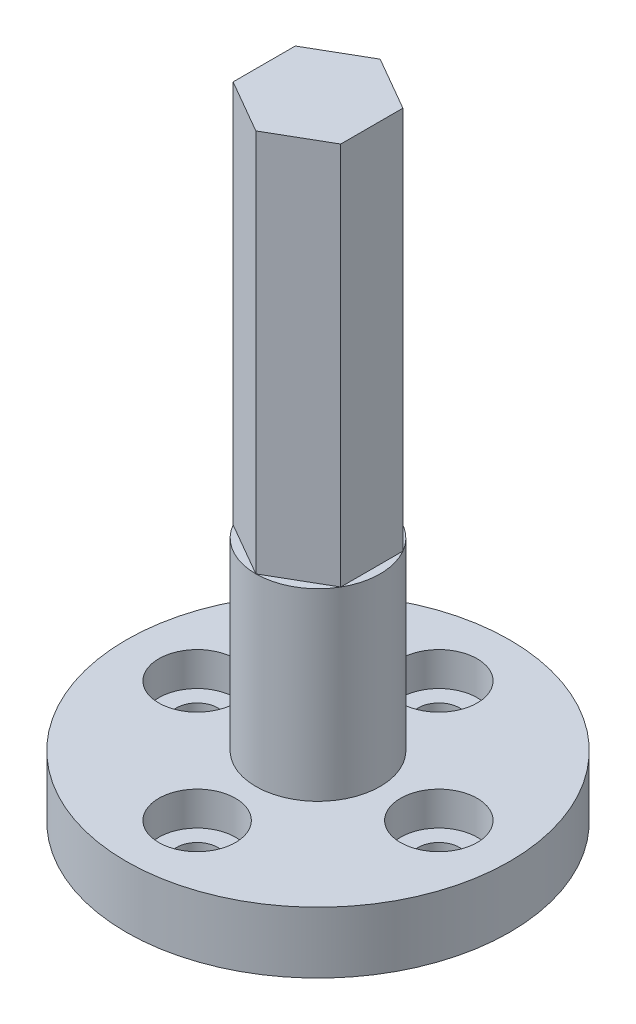
SolidWorks part; units mm, degrees
ref_plane "Alzado" through (0, 0, 0) normal (0, 0, 1) x (1, 0, 0)
ref_plane "Planta" through (0, 0, 0) normal (0, 1, 0) x (1, 0, 0)
ref_plane "Vista lateral" through (0, 0, 0) normal (1, 0, 0) x (0, 0, -1)
sketch "Croquis3" plane through (0, 0, 0) normal (0, 1, 0) x (1, 0, 0)
  circle A0 centre (0, 0) radius 12.5
  dimension "D1" = 25
extrude "Saliente-Extruir1" add sketch "Croquis3" along normal blind 4
sketch "Croquis4" plane through (0, 4, 0) normal (0, 1, 0) x (1, 0, 0)
  circle A0 centre (0, 0) radius 4.05
  dimension "D1" = 8.1
extrude "Saliente-Extruir2" add sketch "Croquis4" along normal blind 37
sketch "Croquis7" plane through (0, 0, 0) normal (0, -1, 0) x (1, 0, 0)
  circle A0 centre (0, 0) radius 12
  dimension "D1" = 24
sketch "Croquis12" plane through (0, 41, 0) normal (0, 1, 0) x (1, 0, 0)
  line L1 (0, 4.05) -> (-3.5074, 2.025)
  line L2 (-3.5074, 2.025) -> (-3.5074, -2.025)
  line L3 (-3.5074, -2.025) -> (0, -4.05)
  line L4 (0, -4.05) -> (3.5074, -2.025)
  line L5 (3.5074, -2.025) -> (3.5074, 2.025)
  line L6 (3.5074, 2.025) -> (0, 4.05)
  circle A0 centre (0, 0) radius 4.05 construction
  circle A1 centre (0, 0) radius 4.05 construction
  circle A2 centre (0, 0) radius 4.05 construction
extrude "Cortar-Extruir7" cut sketch "Croquis12" against normal blind 25 flip side to cut
sketch "Croquis13" plane through (0, 0, 0) normal (0, -1, 0) x (1, 0, 0)
  circle A0 centre (0, 7.875) radius 1.35
  circle A1 centre (7.875, 0) radius 1.35
  circle A2 centre (0, -7.875) radius 1.35
  circle A3 centre (-7.875, 0) radius 1.35
  point P12 (0, 0)
  dimension "D1" = 7.875
  dimension "D3" = 2.7
  dimension "D2" = 4
extrude "Cortar-Extruir8" cut sketch "Croquis13" against normal blind 10
sketch "Croquis14" plane through (0, 4, 0) normal (0, 1, 0) x (1, 0, 0)
  circle A0 centre (0, 7.875) radius 1.35 construction
  circle A1 centre (0, 7.875) radius 1.35 construction
  circle A2 centre (0, 7.875) radius 2.5
  circle A3 centre (7.875, 0) radius 2.5
  circle A4 centre (0, -7.875) radius 2.5
  circle A5 centre (-7.875, 0) radius 2.5
  point P13 (0, 0)
  dimension "D1" = 5
  dimension "D2" = 4
extrude "Cortar-Extruir9" cut sketch "Croquis14" against normal blind 2.2
